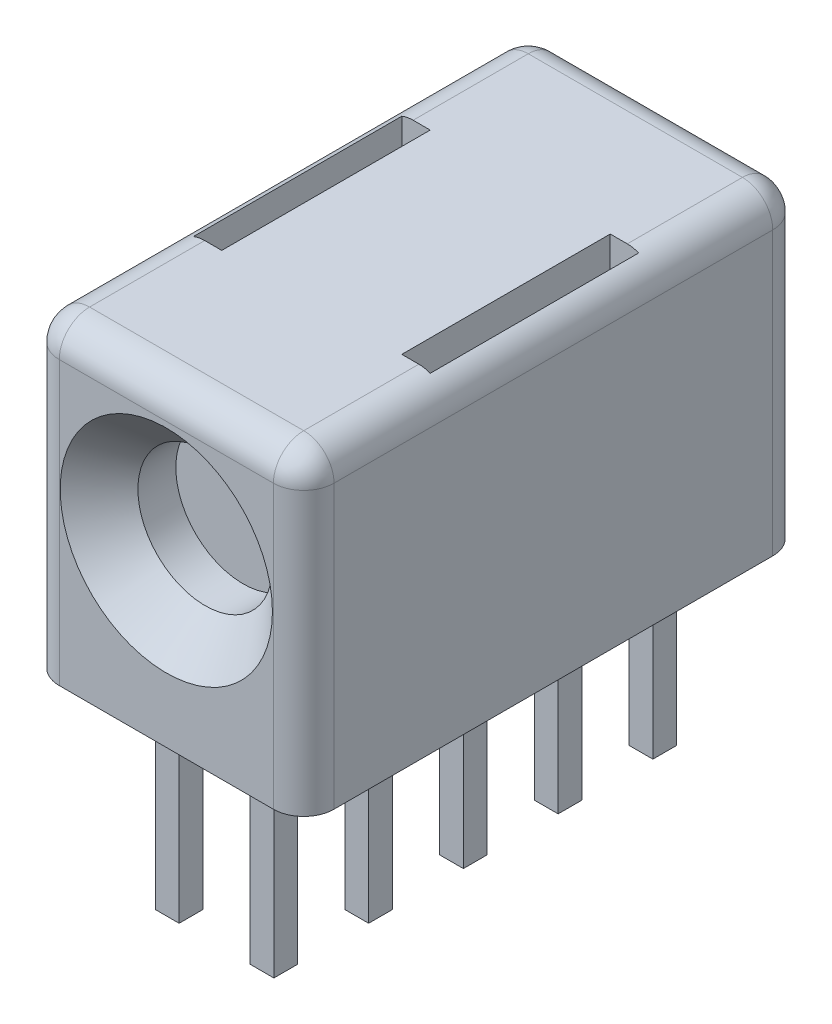
SolidWorks part; units mm, degrees
ref_plane "Front Plane" through (0, 0, 0) normal (0, 0, 1) x (1, 0, 0)
ref_plane "Top Plane" through (0, 0, 0) normal (0, 1, 0) x (1, 0, 0)
ref_plane "Right Plane" through (0, 0, 0) normal (1, 0, 0) x (0, 0, -1)
ref_plane "Plane1" through (-3.683, 0, 0) normal (-1, 0, 0) x (0, -1, 0)
sketch "Sketch1" plane through (-3.683, 0, 0) normal (-1, 0, 0) x (0, -1, 0)
  line L0 (4.572, -13.3858) -> (4.572, 0)
  line L1 (4.572, 0) -> (-3.81, 0)
  line L2 (-3.81, 0) -> (-3.81, -13.3858)
  line L3 (-3.81, -13.3858) -> (4.572, -13.3858)
extrude "Boss-Extrude1" add sketch "Sketch1" against normal blind 7.366
sketch "Sketch2" plane through (0, -4.572, 0) normal (0, -1, 0) x (1, 0, 0)
  line L0 (2.794, -2.5654) -> (2.794, -3.2004)
  line L1 (2.794, -3.2004) -> (-2.794, -3.2004)
  line L2 (-2.794, -3.2004) -> (-2.794, -2.5654)
  line L3 (-2.794, -2.5654) -> (2.794, -2.5654)
extrude "Boss-Extrude2" add sketch "Sketch2" along normal blind 0.635
sketch "Sketch3" plane through (0, -4.572, 0) normal (0, -1, 0) x (1, 0, 0)
  line L0 (2.794, -10.1854) -> (2.794, -10.8204)
  line L1 (2.794, -10.8204) -> (-2.794, -10.8204)
  line L2 (-2.794, -10.8204) -> (-2.794, -10.1854)
  line L3 (-2.794, -10.1854) -> (2.794, -10.1854)
extrude "Boss-Extrude3" add sketch "Sketch3" along normal blind 0.635
sketch "Sketch4" plane through (0, -4.572, 0) normal (0, -1, 0) x (1, 0, 0)
  line L0 (1.5875, -12.0904) -> (0.9525, -12.0904)
  line L1 (0.9525, -12.0904) -> (0.9525, -11.4554)
  line L2 (0.9525, -11.4554) -> (1.5875, -11.4554)
  line L3 (1.5875, -11.4554) -> (1.5875, -12.0904)
extrude "Boss-Extrude4" add sketch "Sketch4" along normal blind 5.207
sketch "Sketch5" plane through (0, -4.572, 0) normal (0, -1, 0) x (1, 0, 0)
  line L0 (-0.9525, -11.4554) -> (-0.9525, -12.0904)
  line L1 (-0.9525, -12.0904) -> (-1.5875, -12.0904)
  line L2 (-1.5875, -12.0904) -> (-1.5875, -11.4554)
  line L3 (-1.5875, -11.4554) -> (-0.9525, -11.4554)
extrude "Boss-Extrude5" add sketch "Sketch5" along normal blind 5.207
sketch "Sketch6" plane through (0, -4.572, 0) normal (0, -1, 0) x (1, 0, 0)
  line L0 (1.5875, -9.5504) -> (0.9525, -9.5504)
  line L1 (0.9525, -9.5504) -> (0.9525, -8.9154)
  line L2 (0.9525, -8.9154) -> (1.5875, -8.9154)
  line L3 (1.5875, -8.9154) -> (1.5875, -9.5504)
extrude "Boss-Extrude6" add sketch "Sketch6" along normal blind 5.207
sketch "Sketch7" plane through (0, -4.572, 0) normal (0, -1, 0) x (1, 0, 0)
  line L0 (-0.9525, -8.9154) -> (-0.9525, -9.5504)
  line L1 (-0.9525, -9.5504) -> (-1.5875, -9.5504)
  line L2 (-1.5875, -9.5504) -> (-1.5875, -8.9154)
  line L3 (-1.5875, -8.9154) -> (-0.9525, -8.9154)
extrude "Boss-Extrude7" add sketch "Sketch7" along normal blind 5.207
sketch "Sketch8" plane through (0, -4.572, 0) normal (0, -1, 0) x (1, 0, 0)
  line L0 (1.5875, -7.0104) -> (0.9525, -7.0104)
  line L1 (0.9525, -7.0104) -> (0.9525, -6.3754)
  line L2 (0.9525, -6.3754) -> (1.5875, -6.3754)
  line L3 (1.5875, -6.3754) -> (1.5875, -7.0104)
extrude "Boss-Extrude8" add sketch "Sketch8" along normal blind 5.207
sketch "Sketch9" plane through (0, -4.572, 0) normal (0, -1, 0) x (1, 0, 0)
  line L0 (-0.9525, -6.3754) -> (-0.9525, -7.0104)
  line L1 (-0.9525, -7.0104) -> (-1.5875, -7.0104)
  line L2 (-1.5875, -7.0104) -> (-1.5875, -6.3754)
  line L3 (-1.5875, -6.3754) -> (-0.9525, -6.3754)
extrude "Boss-Extrude9" add sketch "Sketch9" along normal blind 5.207
sketch "Sketch10" plane through (0, -4.572, 0) normal (0, -1, 0) x (1, 0, 0)
  line L0 (1.5875, -4.4704) -> (0.9525, -4.4704)
  line L1 (0.9525, -4.4704) -> (0.9525, -3.8354)
  line L2 (0.9525, -3.8354) -> (1.5875, -3.8354)
  line L3 (1.5875, -3.8354) -> (1.5875, -4.4704)
extrude "Boss-Extrude10" add sketch "Sketch10" along normal blind 5.207
sketch "Sketch11" plane through (0, -4.572, 0) normal (0, -1, 0) x (1, 0, 0)
  line L0 (-0.9525, -3.8354) -> (-0.9525, -4.4704)
  line L1 (-0.9525, -4.4704) -> (-1.5875, -4.4704)
  line L2 (-1.5875, -4.4704) -> (-1.5875, -3.8354)
  line L3 (-1.5875, -3.8354) -> (-0.9525, -3.8354)
extrude "Boss-Extrude11" add sketch "Sketch11" along normal blind 5.207
sketch "Sketch12" plane through (0, -4.572, 0) normal (0, -1, 0) x (1, 0, 0)
  line L0 (1.5875, -1.9304) -> (0.9525, -1.9304)
  line L1 (0.9525, -1.9304) -> (0.9525, -1.2954)
  line L2 (0.9525, -1.2954) -> (1.5875, -1.2954)
  line L3 (1.5875, -1.2954) -> (1.5875, -1.9304)
extrude "Boss-Extrude12" add sketch "Sketch12" along normal blind 5.207
sketch "Sketch13" plane through (0, -4.572, 0) normal (0, -1, 0) x (1, 0, 0)
  line L0 (-0.9525, -1.2954) -> (-0.9525, -1.9304)
  line L1 (-0.9525, -1.9304) -> (-1.5875, -1.9304)
  line L2 (-1.5875, -1.9304) -> (-1.5875, -1.2954)
  line L3 (-1.5875, -1.2954) -> (-0.9525, -1.2954)
extrude "Boss-Extrude13" add sketch "Sketch13" along normal blind 5.207
sketch "Sketch14" plane through (0, 3.81, 0) normal (0, 1, 0) x (-1, 0, 0)
  line L0 (3.175, -9.4869) -> (3.175, -3.8989)
  line L1 (3.175, -3.8989) -> (2.413, -3.8989)
  line L2 (2.413, -3.8989) -> (2.413, -9.4869)
  line L3 (2.413, -9.4869) -> (3.175, -9.4869)
extrude "Cut-Extrude1" cut sketch "Sketch14" against normal blind 1
sketch "Sketch15" plane through (0, 3.81, 0) normal (0, 1, 0) x (-1, 0, 0)
  line L0 (-3.175, -9.4869) -> (-2.413, -9.4869)
  line L1 (-2.413, -9.4869) -> (-2.413, -3.8989)
  line L2 (-2.413, -3.8989) -> (-3.175, -3.8989)
  line L3 (-3.175, -3.8989) -> (-3.175, -9.4869)
extrude "Cut-Extrude2" cut sketch "Sketch15" against normal blind 1
hole_wizard "Hole1" positions "Sketch17" profile "Sketch16" legacy
sketch "Sketch17" plane through (0, 0, 0) normal (0, 0, 1) x (1, 0, 0)
  point P0 (0, 0)
sketch "Sketch16" plane through (0, 0, 0) normal (1, 0, 0) x (0, -1, 0)
  line L0 (0, 0) -> (0, 2.0574)
  line L1 (0, 2.0574) -> (1.8034, 2.0574)
  line L2 (1.8034, 2.0574) -> (1.8034, 1.0414)
  line L3 (1.8034, 1.0414) -> (2.8448, 0)
  line L4 (2.8448, 0) -> (0, 0)
  line L5 (0, -6.4453) -> (0, 115.525) construction
  line L6 (-1.8034, 1.0414) -> (-2.8448, 0) construction
  dimension "Diameter" = 3.6068
  dimension "Depth" = 2.0574
  dimension "C-Sink Angle" = 90
  dimension "C-Sink Diameter" = 5.6896
hole_wizard "Hole2" positions "Sketch19" profile "Sketch18" legacy
sketch "Sketch19" plane through (0, 0, -13.3858) normal (0, 0, -1) x (-1, 0, 0)
  point P0 (0, 0)
sketch "Sketch18" plane through (0, 0, -13.3858) normal (1, 0, 0) x (0, 1, 0)
  line L0 (0, 0) -> (0, 2.0574)
  line L1 (0, 2.0574) -> (1.8034, 2.0574)
  line L2 (1.8034, 2.0574) -> (1.8034, 1.0414)
  line L3 (1.8034, 1.0414) -> (2.8448, 0)
  line L4 (2.8448, 0) -> (0, 0)
  line L5 (0, -6.4453) -> (0, 115.525) construction
  line L6 (-1.8034, 1.0414) -> (-2.8448, 0) construction
  dimension "Diameter" = 3.6068
  dimension "Depth" = 2.0574
  dimension "C-Sink Angle" = 90
  dimension "C-Sink Diameter" = 5.6896
fillet "Fillet1" radius 0.8128 8 edges at (-3.683, -0.381, -13.3858) (0, 3.81, -13.3858) (3.683, -0.381, -13.3858) (-3.683, -0.381, 0) (-3.683, 3.81, -6.6929) (3.683, 3.81, -6.6929) (0, 3.81, 0) (3.683, -0.381, 0)
